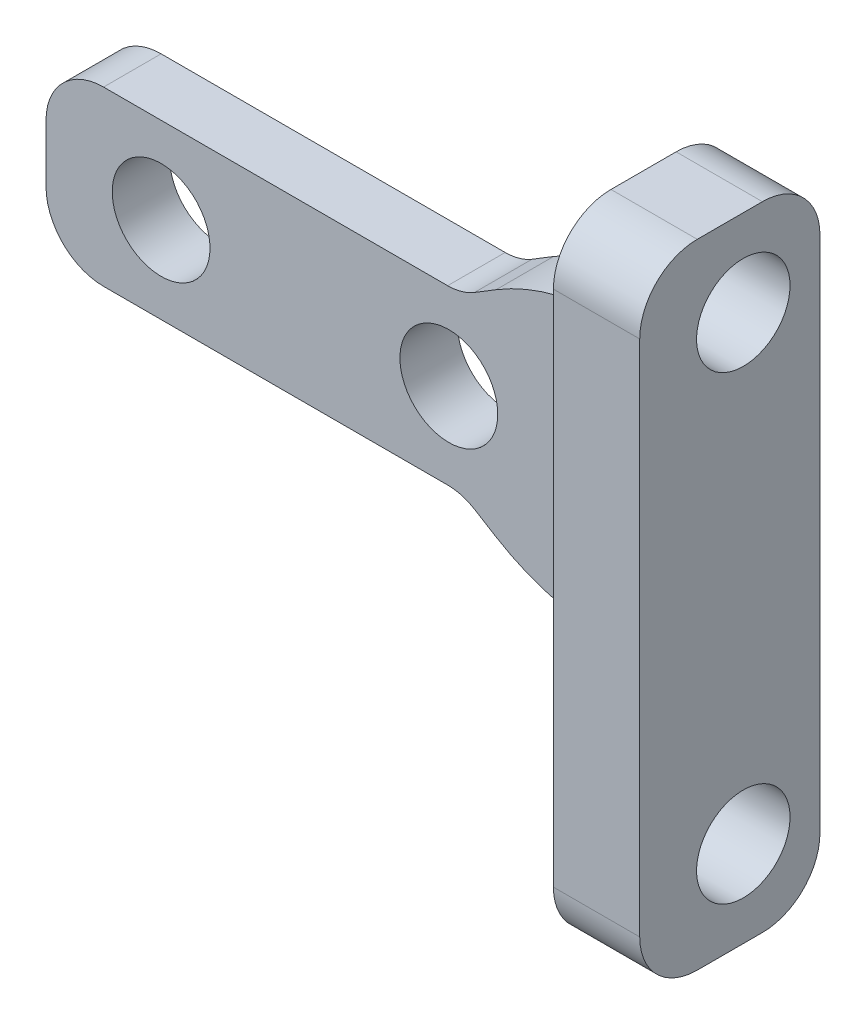
SolidWorks part; units mm, degrees
ref_plane "Front Plane" through (0, 0, 0) normal (0, 0, 1) x (1, 0, 0)
ref_plane "Top Plane" through (0, 0, 0) normal (0, 1, 0) x (1, 0, 0)
ref_plane "Right Plane" through (0, 0, 0) normal (1, 0, 0) x (0, 0, -1)
sketch "Sketch1" plane through (0, 0, 0) normal (0, 0, 1) x (1, 0, 0)
  line L0 (0, 0) -> (10, 0) construction
  line L3 (-4, 3) -> (-4, -3)
  line L4 (-4, -3) -> (9.9583, -3)
  line L7 (20.9, -11) -> (20.9, 11)
  line L10 (9.9583, 3) -> (-4, 3)
  line L11 (20.9, 11.7) -> (20.9, 0.8414) construction
  line L12 (20.9, 11) -> (17.9, 11)
  line L13 (20.9, 11) -> (20.9, -11)
  line L14 (20.9, -11) -> (17.9, -11)
  line L15 (17.9, 11) -> (17.9, -11)
  line L16 (15.5807, 4.83) -> (17.9, 4.83)
  line L17 (-5.099, 3) -> (-15, 3) construction
  line L18 (15.5807, -4.83) -> (17.9, -4.83)
  line L20 (10.8914, 3.2626) -> (11.6424, 3.7217)
  line L22 (10.8914, -3.2626) -> (11.6424, -3.7217)
  circle A2 centre (0, 0) radius 1.5 construction
  circle A3 centre (10, 0) radius 1.5 construction
  arc A4 (9.9583, 3) -> (10.8914, 3.2626) centre (9.9583, 4.7891) ccw
  arc A5 (9.9583, -3) -> (10.8914, -3.2626) centre (9.9583, -4.7891) cw
  arc A6 (11.6424, 3.7217) -> (15.5807, 4.83) centre (15.5807, -2.7214) cw
  arc A7 (11.6424, -3.7217) -> (15.5807, -4.83) centre (15.5807, 2.7214) ccw
  point P7 (-4, 0)
  point P17 (20.9, 0)
  dimension "D2" = 3
  dimension "D1" = 10
  dimension "D3" = 22
  dimension "D5" = 4
  dimension "D6" = 3
extrude "Boss-Extrude1" add sketch "Sketch1" along normal blind 2 contours L15 A4 L10 L3 L4 | L15 L7 region at (8.0458, 0, 0) region at (19.4, 0, 0)
extrude "Boss-Extrude2" add sketch "Sketch1<3>" along normal up to surface (6.265 mm away) contours L12 L15 L14 L7 region at (19.4, 0, 0)
sketch "Sketch1<3>" plane through (0, 0, 0) normal (0, 0, 1) x (1, 0, 0) same geometry as "Sketch1"
hole_wizard "M3 Clearance Hole1" positions "Sketch2" profile "Sketch4" hole size "M3" standard "ANSI Metric" end condition through all
sketch "Sketch2" plane through (0, 0, 2) normal (0, 0, 1) x (1, 0, 0)
  point P0 (0, 0)
  point P5 (10, 0)
sketch "Sketch4" plane through (0, 0, 2) normal (1, 0, 0) x (0, -1, 0)
  line L0 (0, 0) -> (0, 2)
  line L1 (0, 2) -> (1.7, 2)
  line L2 (1.7, 2) -> (1.7, 0)
  line L5 (1.7, 0) -> (0, 0)
  line L11 (0, -6.35) -> (0, 107.95) construction
  dimension "Thru Hole Dia." = 3.4
  dimension "Thru Hole Depth" = 2
fillet "Fillet1" radius 2 6 edges at (-4, 3, 1) (-4, -3, 1) (19.4, -11, 6.265) (19.4, 11, 6.265) (19.4, 11, 0) (19.4, -11, 0)
sketch "Sketch6" plane through (20.9, 0, 0) normal (1, 0, 0) x (0, 0, -1)
  line L0 (0, -11) -> (0, 11) construction
  line L1 (-2.665, 8) -> (-2.665, -8)
  circle A0 centre (-2.665, -8) radius 1.625
  circle A1 centre (-2.665, 8) radius 1.625
  circle A2 centre (-2.665, -8) radius 3.1 construction
  circle A3 centre (-2.665, -8) radius 3.1 construction
  point P5 (0, 0)
  point P11 (-2.665, 0)
  dimension "D2" = 3.25
  dimension "D4" = 16
extrude "Cut-Extrude1" cut sketch "Sketch6" against normal blind 7.5 contours A0 | A1 region at (20.9, -6.8835, 1.5485) region at (20.9, 9.1165, 3.7815)
fillet "Fillet2" radius 1 1 edges at (17.9, 0, 2)
chamfer "Chamfer1" distance 0.5 angle 45 2 edges at (17.9, -4.83, 1.5) (17.9, 4.83, 1.5)
